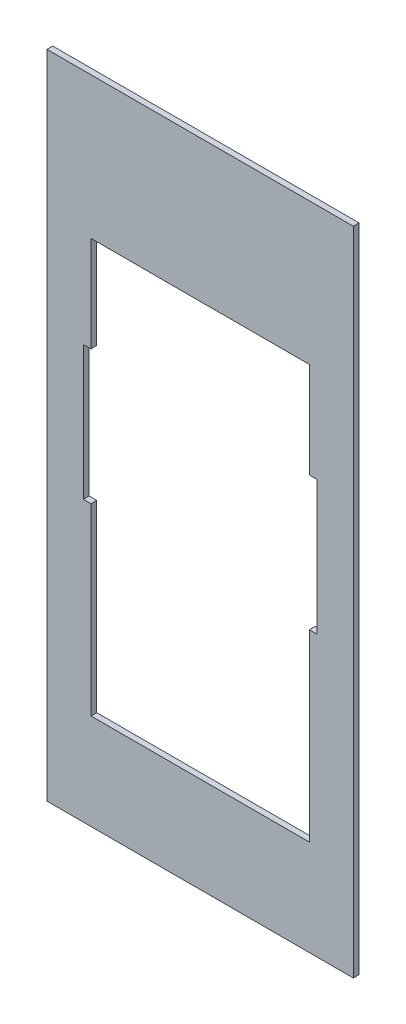
SolidWorks part; units mm, degrees
ref_plane "Front Plane" through (0, 0, 0) normal (0, 0, 1) x (1, 0, 0)
ref_plane "Top Plane" through (0, 0, 0) normal (0, 1, 0) x (1, 0, 0)
ref_plane "Right Plane" through (0, 0, 0) normal (1, 0, 0) x (0, 0, -1)
sketch "Sketch1" plane through (0, 0, 0) normal (0, 0, 1) x (1, 0, 0)
  line L1 (-40, 85) -> (40, 85)
  line L2 (-40, 85) -> (-40, -85)
  line L3 (-40, -85) -> (40, -85)
  line L4 (40, 85) -> (40, -85)
  line L5 (-40, 85) -> (40, -85) construction
  line L6 (-40, -85) -> (40, 85) construction
  line L20 (0, 0) -> (0, 96.4562) construction
  line L21 (0, 0) -> (0, -81.4119) construction
  line L22 (-28.5, -12) -> (-28.5, -60)
  line L23 (-28.5, 48) -> (28.5, 48)
  line L24 (-28.5, 48) -> (-28.5, 23)
  line L25 (-28.5, -60) -> (28.5, -60)
  line L26 (28.5, 48) -> (28.5, 23)
  line L27 (-28.5, 48) -> (28.5, -60) construction
  line L28 (-28.5, -60) -> (28.5, 48) construction
  line L29 (-28.5, 23) -> (-30.5, 23)
  line L31 (-28.5, -12) -> (-30.5, -12)
  line L32 (-30.5, 23) -> (-30.5, -12)
  line L33 (28.5, 23) -> (30.5, 23)
  line L35 (28.5, -12) -> (30.5, -12)
  line L36 (30.5, 23) -> (30.5, -12)
  line L37 (28.5, -12) -> (28.5, -60)
  point P0 (0, 0)
  point P6 (0, -6)
  dimension "D1" = 57
  dimension "D2" = 80
  dimension "D3" = 2
  dimension "D4" = 2
  dimension "D5" = 170
  dimension "D6" = 37
  dimension "D7" = 35
  dimension "D8" = 35
  dimension "D9" = 25
  dimension "D10" = 25
  dimension "D11" = 25
extrude "Boss-Extrude1" add sketch "Sketch1" along normal blind 1.5
